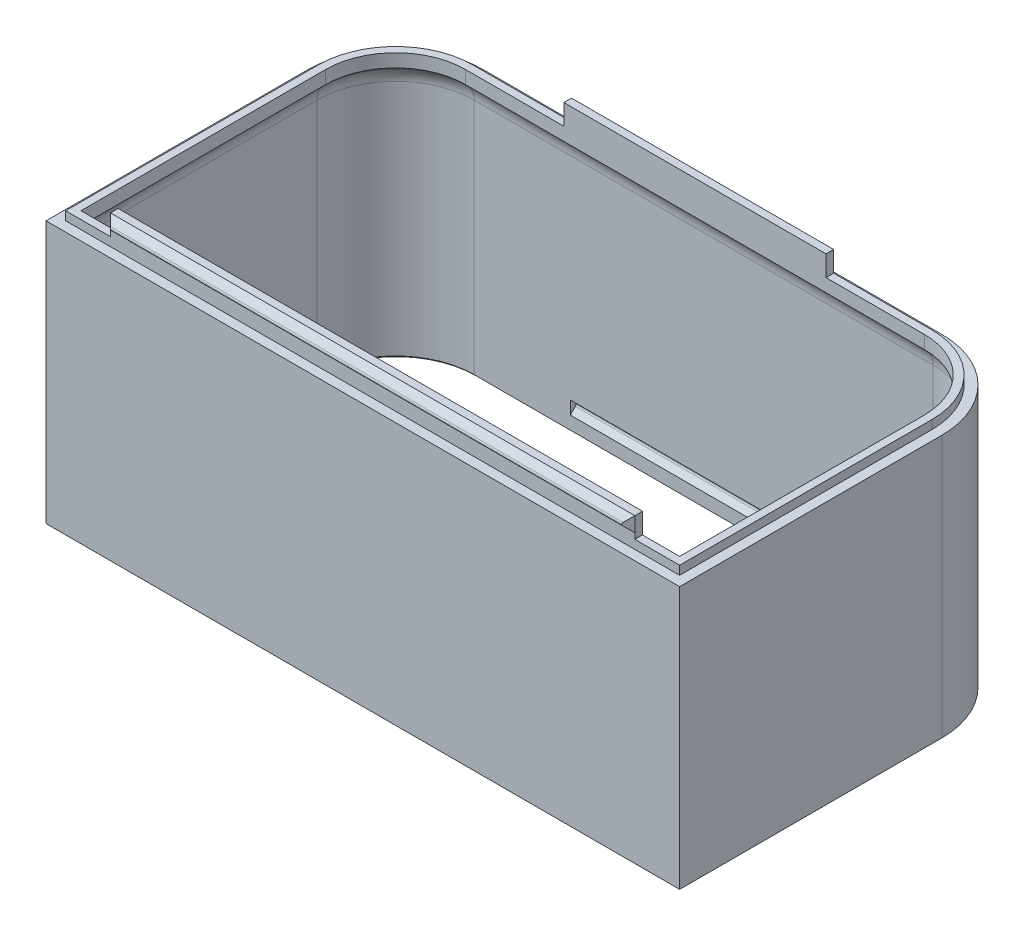
SolidWorks part; units mm, degrees
material "ПК/АБС"
ref_plane "Спереди" through (0, 0, 0) normal (0, 0, 1) x (1, 0, 0)
ref_plane "Сверху" through (0, 0, 0) normal (0, 1, 0) x (1, 0, 0)
ref_plane "Справа" through (0, 0, 0) normal (1, 0, 0) x (0, 0, -1)
sketch "Эскиз1" plane through (0, 0, 0) normal (0, 1, 0) x (1, 0, 0)
  line L0 (-70.5, 2) -> (70.5, 2)
  line L1 (-72.5, 0) -> (72.5, 0)
  line L2 (-72.5, 0) -> (-72.5, 60)
  line L3 (-52.5, 80) -> (52.5, 80)
  line L4 (72.5, 0) -> (72.5, 60)
  line L9 (70.5, 2) -> (70.5, 60)
  line L10 (-52.5, 78) -> (52.5, 78)
  line L11 (-70.5, 2) -> (-70.5, 60)
  arc A0 (72.5, 60) -> (52.5, 80) centre (52.5, 60) ccw
  arc A1 (-52.5, 80) -> (-72.5, 60) centre (-52.5, 60) ccw
  arc A2 (70.5, 60) -> (52.5, 78) centre (52.5, 60) ccw
  arc A3 (-52.5, 78) -> (-70.5, 60) centre (-52.5, 60) ccw
  point P8 (72.5, 80)
  point P11 (-72.5, 80)
  dimension "D3" = 20
  dimension "D1" = 80
  dimension "D2" = 145
  dimension "D4" = 2
extrude "Бобышка-Вытянуть1" add sketch "Эскиз1" along normal blind 60
sketch "Эскиз2" plane through (0, 60, 0) normal (0, 1, 0) x (1, 0, 0)
  line L0 (-68.5, 60) -> (-68.5, 4)
  line L1 (-68.5, 4) -> (68.5, 4)
  line L2 (68.5, 4) -> (68.5, 60)
  line L3 (52.5, 76) -> (-52.5, 76)
  line L4 (-72.5, 60) -> (-72.5, 0)
  line L5 (-72.5, 0) -> (72.5, 0)
  line L6 (72.5, 0) -> (72.5, 60)
  line L7 (52.5, 80) -> (-52.5, 80)
  line L8 (-72.5, 60) -> (-72.5, 0)
  line L9 (-72.5, 0) -> (72.5, 0)
  line L10 (72.5, 0) -> (72.5, 60)
  line L11 (52.5, 80) -> (-52.5, 80)
  arc A0 (68.5, 60) -> (52.5, 76) centre (52.5, 60) ccw
  arc A1 (-52.5, 76) -> (-68.5, 60) centre (-52.5, 60) ccw
  arc A2 (72.5, 60) -> (52.5, 80) centre (52.5, 60) ccw
  arc A3 (-52.5, 80) -> (-72.5, 60) centre (-52.5, 60) ccw
  arc A4 (72.5, 60) -> (52.5, 80) centre (52.5, 60) ccw
  arc A5 (-52.5, 80) -> (-72.5, 60) centre (-52.5, 60) ccw
  dimension "D1" = 0
  dimension "D2" = 4
extrude "Бобышка-Вытянуть2" add sketch "Эскиз2" against normal blind 1
chamfer "Фаска3" distance 2 angle 45 6 edges at (70.5, 59, -31) (65.2279, 59, -72.7279) (0, 59, -78) (-65.2279, 59, -72.7279) (0, 59, -2) (-70.5, 59, -31)
sketch "Эскиз11" plane through (0, 60, 0) normal (0, 1, 0) x (1, 0, 0)
  line L0 (68.5, 4) -> (68.5, 60) construction
  line L1 (-68.5, 4) -> (68.5, 4) construction
  line L2 (-68.5, 60) -> (-68.5, 4) construction
  line L3 (52.5, 76) -> (-52.5, 76) construction
  line L4 (68.5, 4) -> (68.5, 60)
  line L5 (-68.5, 4) -> (68.5, 4)
  line L6 (-68.5, 60) -> (-68.5, 4)
  line L7 (52.5, 76) -> (-52.5, 76)
  line L8 (70.25, 2.25) -> (70.25, 60)
  line L9 (52.5, 77.75) -> (-52.5, 77.75)
  line L10 (-70.25, 60) -> (-70.25, 2.25)
  line L11 (-70.25, 2.25) -> (70.25, 2.25)
  arc A0 (68.5, 60) -> (52.5, 76) centre (52.5, 60) ccw construction
  arc A1 (-52.5, 76) -> (-68.5, 60) centre (-52.5, 60) ccw construction
  arc A2 (68.5, 60) -> (52.5, 76) centre (52.5, 60) ccw
  arc A3 (-52.5, 76) -> (-68.5, 60) centre (-52.5, 60) ccw
  arc A4 (70.25, 60) -> (52.5, 77.75) centre (52.5, 60) ccw
  arc A5 (-52.5, 77.75) -> (-70.25, 60) centre (-52.5, 60) ccw
  dimension "D1" = 1.75
extrude "Бобышка-Вытянуть8" add sketch "Эскиз11" along normal blind 2
sketch "Эскиз12" plane through (0, 0, 0) normal (1, 0, 0) x (0, 0, -1)
  line L0 (76, 59) -> (76, 62) construction
  line L1 (76, 59) -> (76, 62) construction
  line L2 (76, 62) -> (76, 66.7)
  line L3 (76, 66.7) -> (77.75, 66.7)
  line L4 (77.75, 66.7) -> (79.45, 65)
  line L5 (79.45, 65) -> (77.75, 63.3)
  line L6 (77.75, 63.3) -> (77.75, 62)
  line L7 (77.75, 62) -> (76, 62)
  line L9 (80, 60) -> (60, 60) construction
  dimension "D1" = 1.7
  dimension "D2" = 5
extrude "Бобышка-Вытянуть9" add sketch "Эскиз12" along normal mid plane 60
sketch "Эскиз13" plane through (0, 0, 0) normal (1, 0, 0) x (0, 0, -1)
  line L0 (2.25, 62) -> (2.25, 63.3)
  line L1 (2.25, 63.3) -> (0.55, 65)
  line L2 (0.55, 65) -> (2.25, 66.7)
  line L3 (2.25, 66.7) -> (4, 66.7)
  line L4 (4, 66.7) -> (4, 62)
  line L5 (2.25, 62) -> (60, 62) construction
  line L6 (4, 62) -> (2.25, 62)
  line L7 (4, 59) -> (4, 62) construction
  line L8 (4, 59) -> (4, 62) construction
  line L9 (0, 60) -> (60, 60) construction
  dimension "D1" = 5
  dimension "D2" = 1.7
extrude "Бобышка-Вытянуть10" add sketch "Эскиз13" along normal mid plane 120
sketch "Эскиз15" plane through (0, 0, 0) normal (1, 0, 0) x (0, 0, -1)
  line L0 (2, 3.5) -> (2, 6.5)
  line L1 (2, 6.5) -> (0.5, 5)
  line L2 (0.5, 5) -> (2, 3.5)
  line L3 (0, 60) -> (0, 0) construction
  line L4 (0, 0) -> (60, 0) construction
  dimension "D1" = 2
  dimension "D2" = 1.5
  dimension "D3" = 5
extrude "Вырез-Вытянуть2" cut sketch "Эскиз15" against normal mid plane 121
sketch "Эскиз16" plane through (0, 0, 0) normal (1, 0, 0) x (0, 0, -1)
  line L0 (78, 3.5) -> (78, 6.5)
  line L1 (78, 6.5) -> (79.5, 5)
  line L2 (79.5, 5) -> (78, 3.5)
  line L3 (60, 0) -> (80, 0) construction
  dimension "D1" = 2
  dimension "D2" = 1.5
  dimension "D3" = 5
extrude "Вырез-Вытянуть3" cut sketch "Эскиз16" against normal mid plane 61
chamfer "Фаска6" distance 0.5 angle 45 6 edges at (-70.5, 0, -31) (-65.2279, 0, -72.7279) (0, 0, -78) (65.2279, 0, -72.7279) (0, 0, -2) (70.5, 0, -31)
fillet "Скругление3" radius 5 6 edges at (70.5, 57, -31) (65.2279, 57, -72.7279) (0, 57, -78) (-65.2279, 57, -72.7279) (0, 57, -2) (-70.5, 57, -31)
fillet "Скругление4" radius 0.5 2 edges at (0, 5, -0.5) (0, 5, -79.5)
fillet "Скругление5" radius 0.5 2 edges at (0, 65, -79.45) (0, 65, -0.55)
sketch "Эскиз18" plane through (0, 0, 0) normal (0, 0, 1) x (1, 0, 0)
  line L0 (-72.5, 0) -> (72.5, 0) construction
  line L1 (-11, 30) -> (-10, 30)
  line L2 (-11, 30) -> (-11, 0)
  line L3 (-11, 0) -> (-10, 0)
  line L4 (-10, 30) -> (-10, 0)
  line L5 (-10, 30) -> (10, 30) construction
  line L6 (10, 30) -> (11, 30)
  line L7 (10, 30) -> (10, 0)
  line L8 (10, 0) -> (11, 0)
  line L9 (11, 30) -> (11, 0)
  line L10 (0, 0) -> (0, 30) construction
  dimension "D1" = 20
  dimension "D2" = 1
  dimension "D3" = 30
extrude "Вырез-Вытянуть4" [suppressed] cut sketch "Эскиз18" against normal up to surface (2 mm away) up to face at (0, 5, -2)
sketch "Эскиз19" plane through (0, 62, 0) normal (0, 1, 0) x (1, 0, 0)
  line L0 (30, 77.75) -> (28, 79.75)
  line L2 (28, 79.75) -> (30, 79.75)
  line L4 (30, 79.75) -> (30, 77.75)
  line L5 (-30, 77.75) -> (-28, 79.75)
  line L6 (-28, 79.75) -> (-30, 79.75)
  line L7 (-30, 79.75) -> (-30, 77.75)
  line L8 (-60, 2.25) -> (-58, 0.25)
  line L9 (-58, 0.25) -> (-60, 0.25)
  line L10 (-60, 0.25) -> (-60, 2.25)
  line L11 (60, 2.25) -> (60, 0.25)
  line L12 (60, 0.25) -> (58, 0.25)
  line L13 (58, 0.25) -> (60, 2.25)
  dimension "D1" = 2
extrude "Вырез-Вытянуть5" cut sketch "Эскиз19" along normal through all
